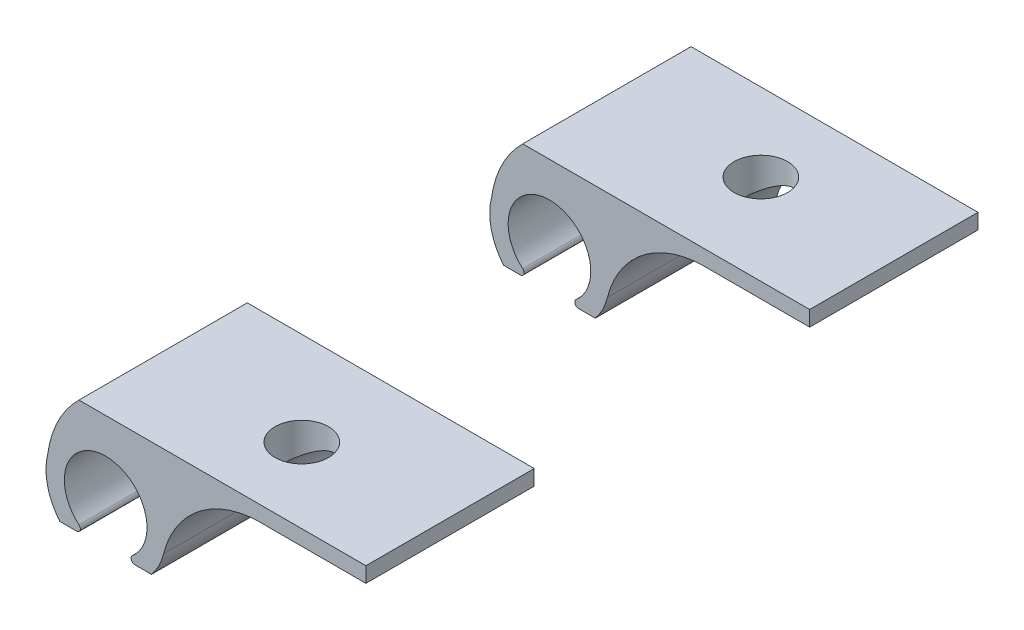
SolidWorks part; units mm, degrees
ref_plane "Front Plane" through (0, 0, 0) normal (0, 0, 1) x (1, 0, 0)
ref_plane "Top Plane" through (0, 0, 0) normal (0, 1, 0) x (1, 0, 0)
ref_plane "Right Plane" through (0, 0, 0) normal (1, 0, 0) x (0, 0, -1)
ref_plane "Плоскость1" through (0, -4, 0) normal (0, 1, 0) x (1, 0, 0)
sketch "Эскиз1" plane through (0, 0, 0) normal (0, 1, 0) x (1, 0, 0)
  line L0 (-40.6, -27.2) -> (40.6, -27.2)
  line L1 (0, 0) -> (44.6, 0) construction
  line L6 (40.6, 27.2) -> (40.6, 23.2) construction
  line L7 (40.6, 27.2) -> (-40.6, 27.2)
  line L11 (-40.6, 27.2) -> (-40.6, 23.2) construction
  line L20 (-44.6, 23.2) -> (-44.6, -23.2)
  line L24 (44.6, -23.2) -> (44.6, 23.2)
  line L51 (-5.4, 27.2) -> (33.6, 27.2)
  arc A0 (-40.6, 27.2) -> (-44.6, 23.2) centre (-40.6, 23.2) ccw
  arc A1 (44.6, 23.2) -> (40.6, 27.2) centre (40.6, 23.2) ccw
  arc A2 (-44.6, -23.2) -> (-40.6, -27.2) centre (-40.6, -23.2) ccw
  arc A3 (40.6, -27.2) -> (44.6, -23.2) centre (40.6, -23.2) ccw
  point P37 (0, 0)
  point P42 (0, 0)
extrude "Бобышка-Вытянуть1" add sketch "Эскиз1" along normal blind 3.9 contours A3 L24 A1 L7 A0 L20 A2 L0 region at (0, 0, 0)
sketch "Эскиз2" plane through (0, -4, 0) normal (0, 1, 0) x (1, 0, 0)
  line L0 (0, 0) -> (0, 45) construction
  line L1 (-45, 45) -> (45, 45) construction
  line L2 (-44.3008, 45) -> (-45, 45) construction
  line L3 (-45, 45) -> (-45, -45) construction
  line L4 (-45, -45) -> (45, -45) construction
  line L5 (45, -45) -> (45, 45) construction
  line L6 (-45, 0) -> (0, 0) construction
  dimension "D1" = 90
  dimension "D2" = 45
  dimension "D3" = 90
  dimension "D4" = 45
sketch "Эскиз3" plane through (0, 0, 0) normal (0, 0, 1) x (1, 0, 0)
  line L0 (-45, -4) -> (45, -4) construction
  line L1 (-45, -4) -> (45, -4) construction
  line L2 (-44.8219, -4) -> (-44.8219, -6.4999) construction
  line L5 (-47.8153, -6.4999) -> (-45.8419, -6.4999)
  line L7 (-43.8019, -6.4999) -> (-41.8285, -6.4999)
  arc A0 (-43.8019, -6.4999) -> (-45.8419, -6.4999) centre (-44.8219, -4) ccw
  arc A1 (-41.8285, -6.4999) -> (-47.8153, -6.4999) centre (-44.8219, -4) ccw
  point P7 (-45.8419, -6.4999)
  point P9 (-43.8019, -6.4999)
  dimension "D1" = 5.4
  dimension "D2" = 7.8
  dimension "D4" = 45
  dimension "D3" = 2.04
  dimension "D5" = 2.9934
  dimension "D6" = 2.4999
extrude "Бобышка-Вытянуть3" add sketch "Эскиз3" along normal mid plane 40
sketch "Эскиз5" plane through (0, 0, 0) normal (0, 0, 1) x (1, 0, 0)
  line L1 (-41.6689, 3.0157) -> (-41.6318, 2.9999)
  line L8 (-45, -4) -> (45, -4) construction
  line L9 (-48.6038, -4.9525) -> (-47.3483, -4.9525)
  line L10 (-42.2954, -4.9525) -> (-41.04, -4.9525)
  line L11 (-36.6416, 0.871) -> (-34.6, 0)
  arc A2 (-42.2954, -4.9525) -> (-47.3483, -4.9525) centre (-44.8219, -4) ccw
  arc A6 (-34.6, 0) -> (-41.04, -4.9525) centre (-34.7077, -6.5233) ccw
  arc A8 (-36.6416, 0.871) -> (-48.6038, -4.9525) centre (-41.6689, -4) ccw
  arc A9 (-43.8019, -6.4999) -> (-45.8419, -6.4999) centre (-44.8219, -4) ccw construction
  arc A10 (-41.8285, -6.4999) -> (-47.8153, -6.4999) centre (-44.8219, -4) ccw construction
  dimension "D1" = 7
  dimension "D2" = 6.5242
  dimension "D3" = 34.7077
  dimension "D4" = 36.6416
extrude "Бобышка-Вытянуть5" add sketch "Эскиз5" along normal mid plane 40 contours L11 A8 L9 A2 L10 A6 region at (-42.3833, -0.3298, 0)
fillet "Скругление1" radius 0.25 2 edges at (-43.8019, -6.4999, 0) (-45.8419, -6.4999, 0)
mirror "Зеркальное отражение1" about plane through (0, 0, 0) normal (1, 0, 0) of "Бобышка-Вытянуть5"
mirror "Зеркальное отражение2" about plane through (0, 0, 0) normal (1, 0, 0) of "Скругление1", "Бобышка-Вытянуть3"
sketch "Эскиз7" plane through (0, 0, 20) normal (0, 0, 1) x (1, 0, 0)
  line L0 (-45, -4) -> (45, -4) construction
  line L1 (49.5, -4) -> (-49.5, -4) construction
  circle A0 centre (-45, -4) radius 5.5
  dimension "D1" = 11
extrude "Вырез-Вытянуть3" cut sketch "Эскиз7" along normal through all
mirror "Зеркальное отражение3" about plane through (0, 0, 0) normal (1, 0, 0) of "Вырез-Вытянуть3" second plane through (0, 0, 0) second plane normal (0, 0, 1)
sketch "Esquisse1" plane through (0, 3.9, 0) normal (0, 1, 0) x (1, 0, 0)
  line L0 (0, 0) -> (0, 45) construction
  line L1 (-44.6, 20) -> (0, 20)
  line L2 (-44.6, 20) -> (-44.6, -20)
  line L3 (-44.6, -20) -> (0, -20)
  line L4 (0, 20) -> (0, -20)
extrude "Enlèv. mat.-Extru.1" cut sketch "Esquisse1" against normal blind 1.54
sketch "Esquisse2" plane through (0, 3.9, 0) normal (0, 1, 0) x (1, 0, 0)
  line L0 (-44.6, 20) -> (-44.6, 27.2)
  line L1 (-44.6, 27.2) -> (51.6, 27.2)
  line L2 (51.6, 27.2) -> (51.6, -27.2)
  line L3 (51.6, -27.2) -> (-44.6, -27.2)
  line L4 (-44.6, -27.2) -> (-44.6, -20)
  line L5 (-44.6, -20) -> (0, -20)
  line L6 (0, -20) -> (0, 20)
  line L7 (0, 20) -> (-44.6, 20)
  line L8 (-40.6, -27.2) -> (40.6, -27.2) construction
  line L10 (40.6, 27.2) -> (-40.6, 27.2) construction
  line L11 (44.6, -23.2) -> (44.6, 23.2) construction
  dimension "D1" = 7
extrude "Enlèv. mat.-Extru.2" cut sketch "Esquisse2" against normal through all
sketch "Esquisse3" plane through (0, 0, 20) normal (0, 0, 1) x (1, 0, 0)
  line L0 (0, 0) -> (0, 2.36) construction
  line L1 (-50, 2.36) -> (0, 2.36)
  line L2 (-50, 2.36) -> (-50, 1)
  line L3 (-50, 1) -> (0, 1)
  line L4 (0, 2.36) -> (0, 1)
  line L5 (0, 0) -> (-34.8154, 0) construction
  line L6 (-44.6, 2.36) -> (0, 2.36) construction
  point P13 (-50, 1.68)
  dimension "D2" = 50
  dimension "D1" = 1
extrude "Enlèv. mat.-Extru.3" cut sketch "Esquisse3" against normal through all
sketch "Esquisse4" plane through (0, 0, 0) normal (0, -1, 0) x (1, 0, 0)
  line L0 (-27.8154, 20) -> (-27.8154, -20)
  line L1 (-27.8154, 20) -> (0, 20)
  line L3 (-27.8154, -20) -> (0, -20)
  line L4 (0, 20) -> (0, -20)
  line L9 (0, 20) -> (-34.8154, 20) construction
  line L10 (-34.8154, -20) -> (0, -20) construction
  line L11 (0, -20) -> (0, 20) construction
  line L12 (-34.8154, 20) -> (-34.8154, -20) construction
  dimension "D1" = 7
extrude "Enlèv. mat.-Extru.4" cut sketch "Esquisse4" against normal through all
sketch "Esquisse5" plane through (0, 1, 0) normal (0, 1, 0) x (1, 0, 0)
  line L0 (-46.5679, 20) -> (-27.8154, 20) construction
  line L1 (-27.8154, -20) -> (-27.8154, 20) construction
  line L2 (-46.5679, -20) -> (-27.8154, -20) construction
  circle A0 centre (-36.9054, 14.9) radius 1.75
  circle A1 centre (-36.9054, -15.1) radius 1.75
  dimension "D1" = 3.5
  dimension "D2" = 3.5
  dimension "D3" = 5.1
  dimension "D4" = 9.09
  dimension "D5" = 9.09
  dimension "D6" = 4.9
extrude "Enlèv. mat.-Extru.5" cut sketch "Esquisse5" against normal through all
sketch "Esquisse6" plane through (0, 1, 0) normal (0, 1, 0) x (1, 0, 0)
  line L0 (-27.8154, -20) -> (-27.8154, 20) construction
  line L1 (-52.8154, 9) -> (-27.8154, 9)
  line L2 (-52.8154, 9) -> (-52.8154, -9)
  line L3 (-52.8154, -9) -> (-27.8154, -9)
  line L4 (-27.8154, 9) -> (-27.8154, -9)
  line L9 (-45, 0) -> (0, 0) construction
  dimension "D1" = 18
  dimension "D2" = 9
  dimension "D3" = 25
extrude "Enlèv. mat.-Extru.6" cut sketch "Esquisse6" against normal through all
